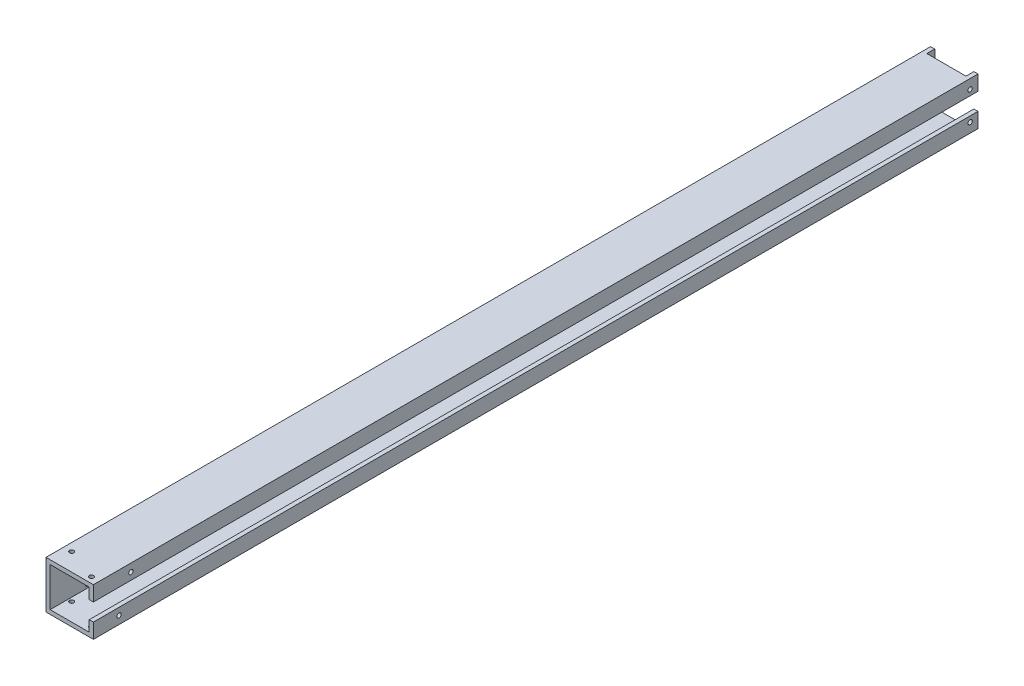
SolidWorks part; units mm, degrees
ref_plane "Front Plane" through (0, 0, 0) normal (1, 0, 0) x (0, 1, 0)
ref_plane "Top Plane" through (0, 0, 0) normal (0, 0, 1) x (0, 1, 0)
ref_plane "Right Plane" through (0, 0, 0) normal (0, 1, 0) x (-1, 0, 0)
sketch "Sketch1" plane through (0, 0, 0) normal (0, 0, 1) x (0, 1, 0)
  line L0 (19.05, -19.05) -> (19.05, 19.05)
  line L1 (19.05, -19.05) -> (-19.05, -19.05)
  line L2 (19.05, -19.05) -> (19.05, 19.05)
  line L3 (19.05, 19.05) -> (-19.05, 19.05)
  line L4 (-19.05, -19.05) -> (-19.05, 19.05)
  line L5 (19.05, -19.05) -> (-19.05, 19.05) construction
  line L6 (19.05, 19.05) -> (-19.05, -19.05) construction
  line L7 (19.05, 19.05) -> (-19.05, 19.05)
  line L8 (-19.05, -19.05) -> (-19.05, 19.05)
  line L9 (19.05, -19.05) -> (-19.05, -19.05)
  line L10 (15.7163, 15.7163) -> (-15.7162, 15.7163)
  line L11 (-15.7162, -15.7163) -> (-15.7162, 15.7163)
  line L12 (15.7163, -15.7162) -> (-15.7162, -15.7163)
  line L13 (15.7163, -15.7162) -> (15.7163, 15.7163)
  line L14 (-6.985, -15.7162) -> (-6.985, -19.05)
  line L15 (6.985, -15.7163) -> (6.985, -19.05)
  line L16 (-15.7162, -15.7163) -> (-6.985, -15.7162)
  line L17 (-6.985, -17.3831) -> (-19.05, -17.3831) construction
  line L18 (6.985, -17.3831) -> (19.05, -17.3831) construction
  point P0 (0, 0)
  dimension "D1" = 38.1
  dimension "D4" = 13.97
  dimension "D3" = 31.4325
  dimension "D2" = 0
extrude "Boss-Extrude1" add sketch "Sketch1" along normal blind 711.2 contours L4 L1 L0 L3 L13 L12 L11 L10 region at (18.5112, 13.0175, 0)
sketch "Sketch6" plane through (0, 0, 0) normal (0, 0, 1) x (0, 1, 0)
  line L1 (26.9875, -26.9875) -> (-26.9875, -26.9875) construction
  line L2 (26.9875, -26.9875) -> (26.9875, 26.9875) construction
  line L3 (26.9875, 26.9875) -> (-26.9875, 26.9875) construction
  line L4 (-26.9875, -26.9875) -> (-26.9875, 26.9875) construction
  line L5 (26.9875, -26.9875) -> (-26.9875, 26.9875) construction
  line L6 (26.9875, 26.9875) -> (-26.9875, -26.9875) construction
  line L11 (-26.9875, 25.8156) -> (-16.9875, 25.8156)
  line L12 (-26.9875, 25.8156) -> (-26.9875, 21.8156)
  line L13 (-26.9875, 21.8156) -> (-16.9875, 21.8156)
  line L14 (-16.9875, 25.8156) -> (-16.9875, 21.8156)
  line L15 (-23.4875, 25.8156) -> (-20.4875, 25.8156)
  line L16 (-23.4875, 25.8156) -> (-23.4875, -2.5726)
  line L17 (-23.4875, -2.5726) -> (-20.4875, -2.5726)
  line L18 (-20.4875, 25.8156) -> (-20.4875, -2.5726)
  point P0 (0, 0)
  point P14 (-21.9875, 25.8156)
  point P15 (-21.9875, 25.8156)
  dimension "D1" = 53.975
  dimension "D2" = 4
  dimension "D3" = 10
  dimension "D4" = 3
sketch "Sketch7" plane through (0, 0, 0) normal (0, 1, 0) x (-1, 0, 0)
  line L0 (-19.05, 711.2) -> (19.05, 711.2) construction
  line L1 (-12.7, 708.1875) -> (-12.7, 704.6875) construction
  line L2 (12.7, 696.9125) -> (-12.7, 696.9125) construction
  line L3 (12.7, 696.9125) -> (12.7, 706.4375) construction
  line L4 (12.7, 706.4375) -> (-12.7, 706.4375) construction
  line L5 (-12.7, 696.9125) -> (-12.7, 706.4375) construction
  line L6 (12.7, 696.9125) -> (-12.7, 706.4375) construction
  line L7 (12.7, 706.4375) -> (-12.7, 696.9125) construction
  line L8 (-19.05, 711.2) -> (-19.05, 0) construction
  circle A0 centre (-12.7, 706.4375) radius 1.75
  circle A1 centre (12.7, 696.9125) radius 1.75
  point P0 (0, 711.2)
  point P2 (0, 701.675)
  dimension "D2" = 3.5
  dimension "D1" = 9.525
  dimension "D3" = 4.7625
  dimension "D4" = 6.35
extrude "Cut-Extrude2" cut sketch "Sketch7" along normal blind 70.104 and the other way blind 58.42
sketch "Sketch8" plane through (0, 19.05, 0) normal (0, 1, 0) x (-1, 0, 0)
  line L0 (-19.05, 0) -> (19.05, 0) construction
  line L1 (15.7163, -6.35) -> (-15.7162, -6.35)
  line L2 (15.7163, -6.35) -> (15.7163, 6.35)
  line L3 (15.7163, 6.35) -> (-15.7162, 6.35)
  line L4 (-15.7162, -6.35) -> (-15.7162, 6.35)
  line L5 (15.7163, -6.35) -> (-15.7162, 6.35) construction
  line L6 (15.7163, 6.35) -> (-15.7162, -6.35) construction
  point P0 (0, 0)
  dimension "1.25" = 31.4325
  dimension "D2" = 6.35
extrude "Cut-Extrude3" cut sketch "Sketch8" against normal blind 71.882
sketch "Sketch9" plane through (19.05, 0, 0) normal (1, 0, 0) x (0, 1, 0)
  line L0 (19.05, 0) -> (6.985, 0) construction
  line L1 (-6.985, 0) -> (-19.05, 0) construction
  line L2 (19.05, 0) -> (6.985, 0) construction
  line L3 (-6.985, 0) -> (-19.05, 0) construction
  line L4 (15.7163, 6.35) -> (19.05, 6.35) construction
  line L5 (-19.05, 6.35) -> (-15.7163, 6.35) construction
  line L6 (15.7163, 6.35) -> (19.05, 6.35) construction
  line L7 (-19.05, 6.35) -> (-15.7163, 6.35) construction
  line L10 (0, 0) -> (0, 6.35) construction
  circle A0 centre (-11.43, 6.35) radius 1.75
  circle A2 centre (11.43, 6.35) radius 1.75
  point P12 (0, 0)
  point P13 (0, 0)
  point P15 (-11.43, 6.35)
  dimension "D2" = 3.5
  dimension "D3" = 6.35
  dimension "D1" = 0
  dimension "D4" = 11.43
extrude "Cut-Extrude4" cut sketch "Sketch9" against normal blind 68.326
sketch "Sketch10" plane through (19.05, 0, 0) normal (1, 0, 0) x (0, 1, 0)
  line L0 (-12.7, 692.3125) -> (-12.7, 688.8125) construction
  line L1 (12.7, 681.0375) -> (-12.7, 681.0375) construction
  line L2 (12.7, 681.0375) -> (12.7, 690.5625) construction
  line L3 (12.7, 690.5625) -> (-12.7, 690.5625) construction
  line L4 (-12.7, 681.0375) -> (-12.7, 690.5625) construction
  line L5 (12.7, 681.0375) -> (-12.7, 690.5625) construction
  line L6 (12.7, 690.5625) -> (-12.7, 681.0375) construction
  line L8 (15.7163, 711.2) -> (-15.7162, 711.2) construction
  line L9 (-15.7162, 711.2) -> (-15.7163, 6.35) construction
  line L10 (-15.7162, 711.2) -> (-15.7163, 6.35) construction
  circle A0 centre (-12.7, 690.5625) radius 1.75
  circle A1 centre (12.7, 681.0375) radius 1.75
  point P0 (0, 685.8)
  point P1 (0, 685.8)
  point P13 (0, 711.2)
  dimension "D2" = 3.5
  dimension "D1" = 9.525
  dimension "D3" = 25.4
  dimension "D4" = 25.4
extrude "Cut-Extrude5" cut sketch "Sketch10" against normal blind 12.7
ref_axis "Axis1" through (0, 0, 746.76) along (0, 0, -1)
pattern_circular "CirPattern1" count 3 every 180 about axis through (0, 0, 746.76) along (0, 0, -1) of "Cut-Extrude5"
